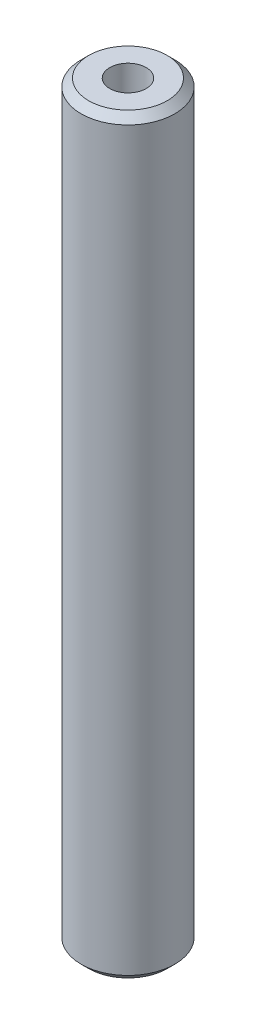
SolidWorks part; units mm, degrees
ref_plane "Front Plane" through (0, 0, 0) normal (0, 0, 1) x (1, 0, 0)
ref_plane "Top Plane" through (0, 0, 0) normal (0, 1, 0) x (1, 0, 0)
ref_plane "Right Plane" through (0, 0, 0) normal (1, 0, 0) x (0, 0, -1)
sketch "Sketch1" plane through (0, 0, 0) normal (0, 1, 0) x (1, 0, 0)
  circle A0 centre (0, 0) radius 22.5
  dimension "SHAFT_OD" = 45
extrude "Boss-Extrude1" add sketch "Sketch1" along normal blind 361.1709
sketch "Sketch2" plane through (0, 0, 0) normal (0, 1, 0) x (1, 0, 0)
  circle A0 centre (0, 0) radius 8.7532
  dimension "BORE_D" = 17.5064
extrude "Cut-Extrude1" cut sketch "Sketch2" along normal through all
chamfer "Chamfer1" distance 3.6307 angle 45 2 edges at (0, 361.1709, 22.5) (0, 0, 22.5)
